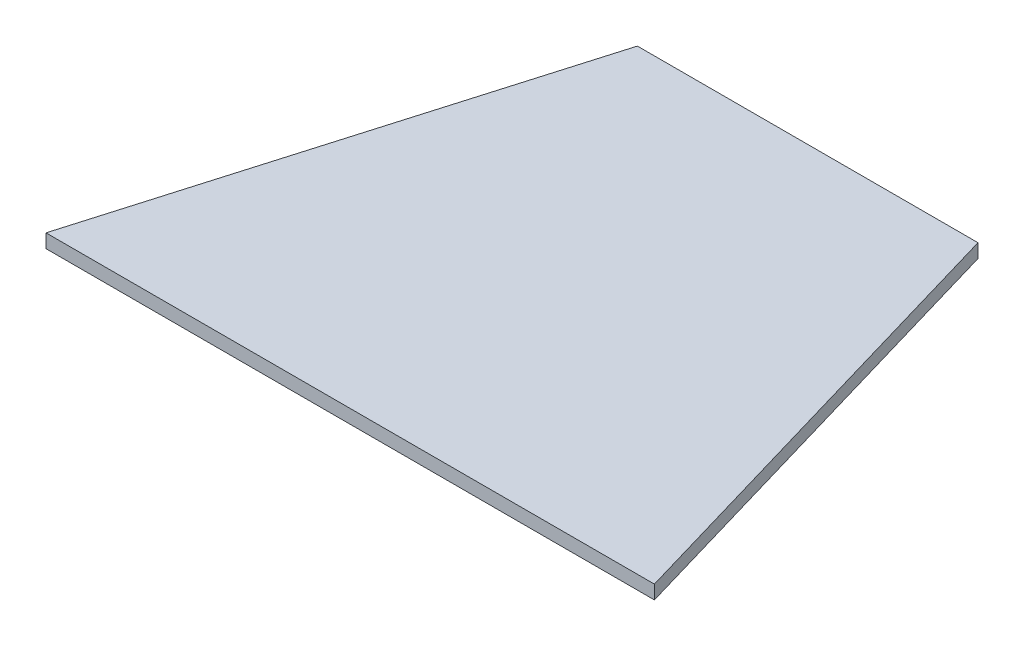
SolidWorks part; units mm, degrees
ref_plane "Front Plane" through (0, 0, 0) normal (0, 0, 1) x (1, 0, 0)
ref_plane "Top Plane" through (0, 0, 0) normal (0, 1, 0) x (1, 0, 0)
ref_plane "Right Plane" through (0, 0, 0) normal (1, 0, 0) x (0, 0, -1)
sketch "Sketch1" plane through (0, 0, 0) normal (0, 1, 0) x (1, 0, 0)
  line L0 (0, 0) -> (133, 0)
  line L1 (0, 0) -> (29.2799, 100)
  line L2 (133, 0) -> (103.739, 100)
  line L3 (66.5, 0) -> (66.5, 100) construction
  line L4 (29.2799, 100) -> (103.739, 100)
extrude "Boss-Extrude1" add sketch "Sketch1" along normal blind 3
